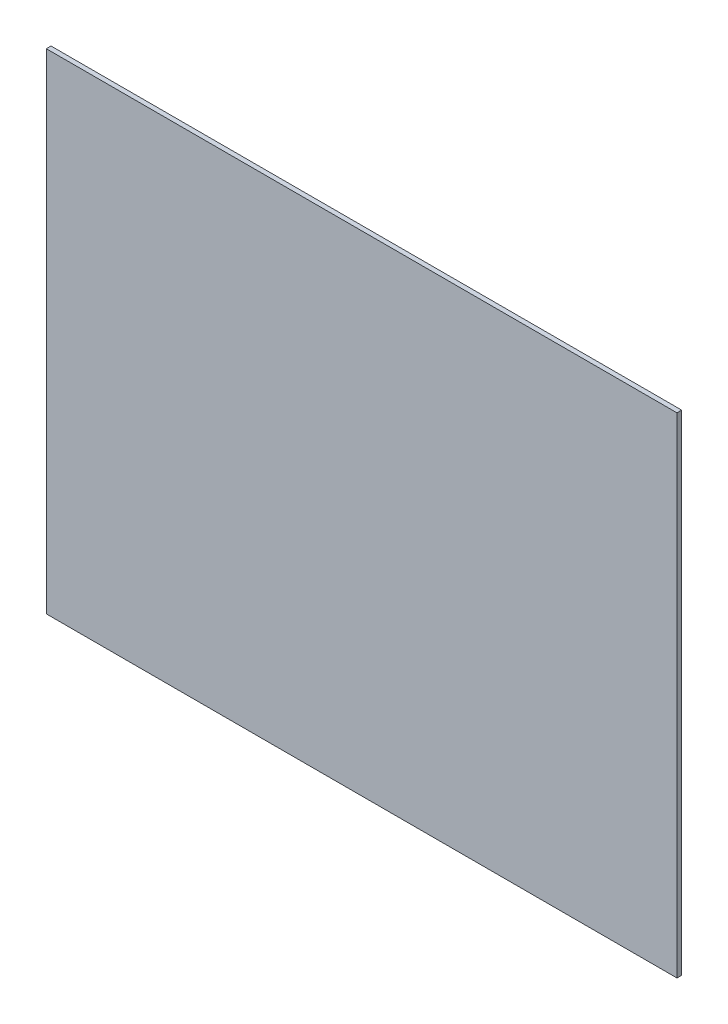
SolidWorks part; units mm, degrees
material "Acrylic (Medium-high impact)"
ref_plane "Front Plane" through (0, 0, 0) normal (0, 0, 1) x (1, 0, 0)
ref_plane "Top Plane" through (0, 0, 0) normal (0, 1, 0) x (1, 0, 0)
ref_plane "Right Plane" through (0, 0, 0) normal (1, 0, 0) x (0, 0, -1)
sketch "Sketch1" plane through (0, 0, 0) normal (0, 0, 1) x (1, 0, 0)
  line L1 (-268, -208) -> (268, -208)
  line L2 (-268, -208) -> (-268, 208)
  line L3 (-268, 208) -> (268, 208)
  line L4 (268, -208) -> (268, 208)
  line L5 (-268, -208) -> (268, 208) construction
  line L6 (-268, 208) -> (268, -208) construction
  point P0 (0, 0)
  dimension "D1" = 536
  dimension "D2" = 416
extrude "Boss-Extrude1" add sketch "Sketch1" along normal mid plane 4
